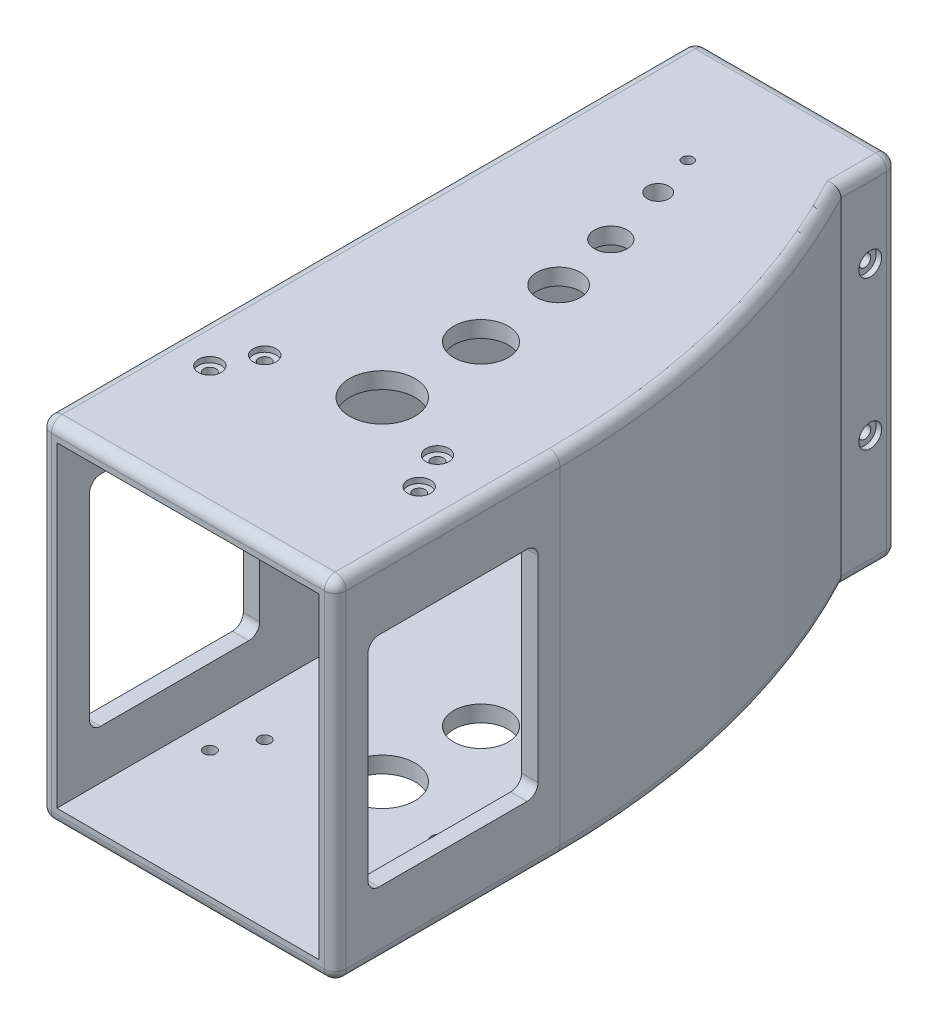
SolidWorks part; units mm, degrees
material "Custom Plastic"
ref_plane "Front Plane" through (0, 0, 0) normal (0, 0, 1) x (1, 0, 0)
ref_plane "Top Plane" through (0, 0, 0) normal (0, 1, 0) x (1, 0, 0)
ref_plane "Right Plane" through (0, 0, 0) normal (1, 0, 0) x (0, 0, -1)
sketch "Sketch3" plane through (0, 0, 0) normal (0, 1, 0) x (1, 0, 0)
  line L0 (0, 0) -> (54, 0)
  line L1 (54, 0) -> (54, 41.2013)
  line L2 (31, 120) -> (0, 120)
  line L3 (0, 120) -> (0, 0)
  arc A0 (54, 41.2013) -> (31, 120) centre (-92.4833, 41.2013) ccw
  dimension "D1" = 54
  dimension "D2" = 31
  dimension "D3" = 120
extrude "Boss-Extrude1" add sketch "Sketch3" along normal blind 64
sketch "Sketch5" plane through (0, 64, 0) normal (0, 1, 0) x (1, 0, 0)
  line L0 (31, 120) -> (37.0293, 120)
  line L1 (37.0293, 120) -> (37.0293, 109.64)
  arc A0 (54, 41.2013) -> (31, 120) centre (-92.4833, 41.2013) ccw construction
  arc A1 (31, 120) -> (37.0293, 109.64) centre (31, 113.0656) ccw
extrude "Boss-Extrude2" add sketch "Sketch5" against normal up to surface (64 mm away) up to face at (28.9265, 0, -56.5691)
shell "Shell1" thickness 3 removed face at (27, 32, 0)
fillet "Fillet1" radius 2 8 edges at (49.694, 0, -76.457) (49.694, 64, -76.457) (18.5146, 0, -120) (18.5146, 64, -120) (54, 0, -20.6007) (54, 64, -20.6007) (0, 0, -60) (0, 64, -60)
sketch "Sketch6" plane through (0, 0, -120) normal (0, 0, -1) x (-1, 0, 0)
  line L0 (0, 62) -> (-37.0293, 62) construction
  line L1 (-31.9074, 34) -> (-3, 34)
  line L2 (-31.9074, 34) -> (-31.9074, 59)
  line L3 (-31.9074, 59) -> (-3, 59)
  line L4 (-3, 34) -> (-3, 59)
  line L5 (-31.9074, 34) -> (-3, 59) construction
  line L6 (-31.9074, 59) -> (-3, 34) construction
  line L7 (0, 62) -> (0, 2) construction
  point P0 (-17.4537, 46.5)
  dimension "D1" = 3
  dimension "D2" = 3
  dimension "D3" = 25
extrude "Cut-Extrude1" cut sketch "Sketch6" against normal blind 64
sketch "Sketch8" plane through (37.0293, 0, 0) normal (1, 0, 0) x (0, 0, -1)
  line L0 (120, 2) -> (120, 62) construction
  circle A0 centre (115, 48.9095) radius 2.1
  circle A1 centre (115, 21.6579) radius 2.1
  dimension "D1" = 4.2
  dimension "D2" = 4.2
  dimension "D3" = 5
extrude "Cut-Extrude2" cut sketch "Sketch8" against normal blind 1
fillet "Fillet2" radius 2 13 edges at (0.5858, 63.4142, 0) (0, 32, 0) (0.5858, 0.5858, 0) (27, 0, 0) (53.4142, 0.5858, 0) (54, 32, 0) (53.4142, 63.4142, 0) (37.0293, 0, -111.6238) (37.0293, 0.5858, -119.4142) (37.0293, 32, -120) (37.0293, 63.4142, -119.4142) (27, 64, 0) (37.0293, 64, -111.6238)
fillet "Fillet3" radius 2 3 edges at (0.5858, 63.4142, -119.4142) (0.5858, 0.5858, -119.4142) (0, 32, -120)
fillet "Fillet4" radius 2 4 edges at (3, 34, -118.5) (31.9074, 34, -118.5) (31.9074, 59, -118.5) (3, 59, -118.5)
sketch "Sketch9" plane through (37.0293, 0, 0) normal (1, 0, 0) x (0, 0, -1)
  circle A0 centre (115, 48.9095) radius 1.1
  circle A1 centre (115, 21.6579) radius 1.1
  dimension "D1" = 2.2
  dimension "D2" = 2.2
extrude "Cut-Extrude3" cut sketch "Sketch9" against normal through all
sketch "Sketch10" plane through (0, 0, 0) normal (-1, 0, 0) x (0, 0, 1)
  circle A0 centre (-115, 48.9095) radius 2.1
  circle A1 centre (-115, 21.6579) radius 2.1
  dimension "D1" = 4.2
  dimension "D2" = 4.2
extrude "Cut-Extrude4" cut sketch "Sketch10" against normal blind 1
sketch "Sketch12" plane through (0, 64, 0) normal (0, 1, 0) x (1, 0, 0)
  line L0 (27, 2) -> (27, 41.1991) construction
  line L1 (2, 2) -> (52, 2) construction
  circle A0 centre (7.8252, 23.2099) radius 2.1
  circle A1 centre (11.172, 29.9036) radius 2.1
  dimension "D1" = 4.2
  dimension "D2" = 4.2
extrude "Cut-Extrude5" cut sketch "Sketch12" against normal blind 1
sketch "Sketch13" plane through (0, 64, 0) normal (0, 1, 0) x (1, 0, 0)
  circle A0 centre (7.8252, 23.2099) radius 1.1
  circle A1 centre (11.172, 29.9036) radius 1.1
  dimension "D1" = 2.2
  dimension "D2" = 2.2
extrude "Cut-Extrude6" cut sketch "Sketch13" against normal through all
sketch "Sketch14" plane through (0, 64, 0) normal (0, 1, 0) x (1, 0, 0)
  line L0 (27, 2) -> (27, 37.0116) construction
  line L1 (2, 2) -> (52, 2) construction
sketch "Sketch16" plane through (0, 0, -117) normal (0, 0, 1) x (1, 0, 0)
  line L0 (27, 62) -> (27, 14.4836) construction
  line L1 (52, 62) -> (2, 62) construction
ref_plane "Plane1" through (27, 0, 0) normal (-1, 0, 0) x (0, 0, 1)
mirror "Mirror1" about plane through (27, 0, 0) normal (-1, 0, 0) of "Cut-Extrude6", "Cut-Extrude5"
sketch "Sketch17" plane through (0, 0, -117) normal (0, 0, 1) x (1, 0, 0)
  line L0 (34.0293, 32) -> (56.7152, 32) construction
  line L1 (34.0293, 3) -> (34.0293, 61) construction
sketch "Sketch18" plane through (0, 0, 0) normal (0, -1, 0) x (1, 0, 0)
  circle A0 centre (7.8252, -23.2099) radius 2.1
  circle A1 centre (11.172, -29.9036) radius 2.1
  circle A2 centre (42.828, -29.9036) radius 2.1
  circle A3 centre (46.1748, -23.2099) radius 2.1
  dimension "D1" = 4.2
  dimension "D2" = 4.2
  dimension "D3" = 4.2
  dimension "D4" = 4.2
extrude "Cut-Extrude7" cut sketch "Sketch18" against normal blind 1
sketch "Sketch19" plane through (0, 0, 0) normal (-1, 0, 0) x (0, 0, 1)
  line L0 (-2, 32) -> (-118, 32) construction
  line L1 (-2, 2) -> (-2, 62) construction
  line L2 (-118, 62) -> (-118, 2) construction
  text T0 "                            SMART METHODS"
extrude "Cut-Extrude8" cut sketch "Sketch19" against normal blind 0.3
sketch "Sketch21" plane through (0, 64, 0) normal (0, 1, 0) x (1, 0, 0)
  line L0 (28.627, 33.9953) -> (31.2938, 61.488) construction
  line L1 (31.2938, 61.488) -> (18.9803, 99.6147) construction
  circle A0 centre (28.627, 33.9953) radius 6
  circle A1 centre (28.8537, 51.8609) radius 5
  circle A2 centre (26.9382, 67.9921) radius 4
  circle A3 centre (24.4898, 80.0045) radius 3
  circle A4 centre (21.3819, 91.7911) radius 2
  circle A5 centre (18.9803, 99.6147) radius 1
  spline S0 degree 2 poles (28.627, 33.9953) (31.2938, 61.488) (18.9803, 99.6147) knots 0 0 0 1 1 1
  dimension "D1" = 12
  dimension "D2" = 10
  dimension "D3" = 8
  dimension "D4" = 6
  dimension "D5" = 4
  dimension "D6" = 2
extrude "Cut-Extrude9" cut sketch "Sketch21" against normal through all and the other way blind 10 contours A0 | A1 | A2 | A3 | A4 | A5
sketch "Sketch22" plane through (54, 0, 0) normal (1, 0, 0) x (0, 0, -1)
  line L0 (2, 62) -> (2, 2) construction
  line L1 (6, 12) -> (37.1589, 12)
  line L2 (6, 12) -> (6, 52)
  line L3 (6, 52) -> (37.1589, 52)
  line L4 (37.1589, 12) -> (37.1589, 52)
  line L5 (6, 12) -> (37.1589, 52) construction
  line L6 (6, 52) -> (37.1589, 12) construction
  line L8 (41.2013, 62) -> (2, 62) construction
  line L10 (2, 2) -> (41.2013, 2) construction
  point P0 (21.5794, 32)
  dimension "D1" = 4
  dimension "D2" = 10
  dimension "D3" = 10
extrude "Cut-Extrude10" cut sketch "Sketch22" against normal through all
fillet "Fillet5" radius 2 8 edges at (1.5, 12, -37.1589) (1.5, 12, -6) (1.5, 52, -6) (1.5, 52, -37.1589) (52.5, 52, -37.1589) (52.5, 12, -37.1589) (52.5, 12, -6) (52.5, 52, -6)
